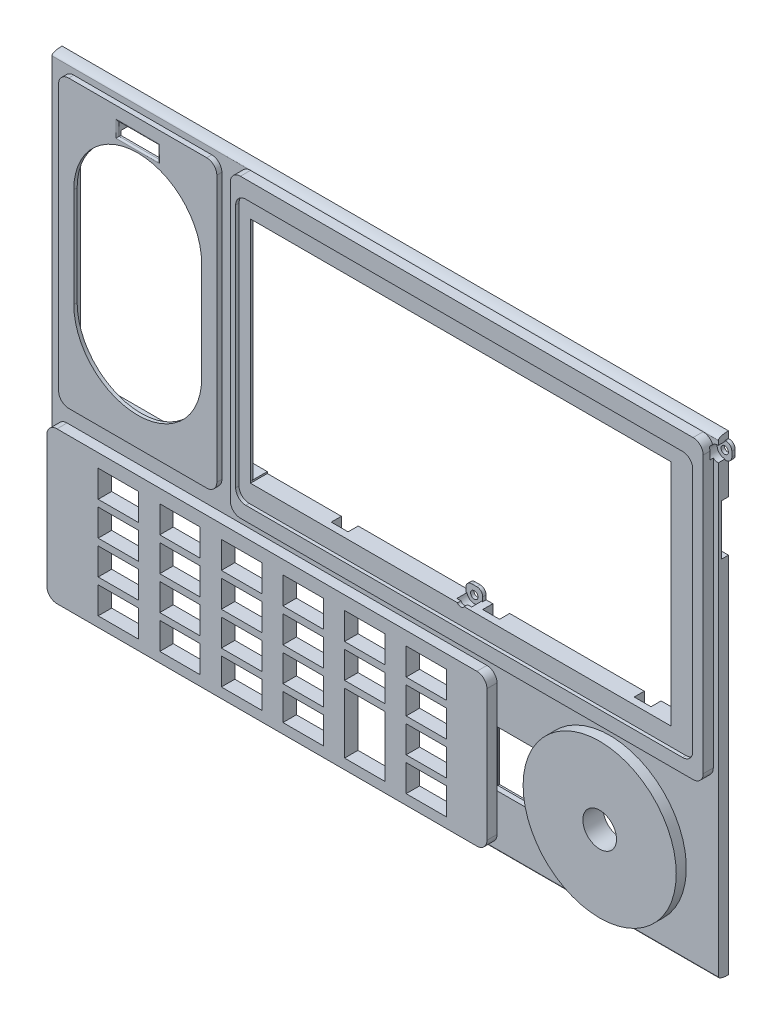
SolidWorks part; units mm, degrees
ref_plane "Front Plane" through (0, 0, 0) normal (0, 0, 1) x (1, 0, 0)
ref_plane "Top Plane" through (0, 0, 0) normal (0, 1, 0) x (1, 0, 0)
ref_plane "Right Plane" through (0, 0, 0) normal (1, 0, 0) x (0, 0, -1)
sketch "Sketch1" plane through (0, 0, 0) normal (0, 0, 1) x (1, 0, 0)
  line L1 (99, -70) -> (-99, -70)
  line L2 (99, -70) -> (99, 70)
  line L3 (99, 70) -> (-99, 70)
  line L4 (-99, -70) -> (-99, 70)
  line L5 (99, -70) -> (-99, 70) construction
  line L6 (99, 70) -> (-99, -70) construction
  point P0 (0, 0)
  dimension "D1" = 198
  dimension "D2" = 140
extrude "main_body" add sketch "Sketch1" along normal blind 3
fillet "long_corners" radius 3 2 edges at (0, 70, 3) (0, -70, 3) second distance 1 first distance on face at (0, 70, 1.5) first distance on face at (0, -70, 1.5)
sketch "Sketch2" plane through (0, 0, 3) normal (0, 0, 1) x (1, 0, 0)
  line L0 (-99, 24.75) -> (99, 24.75) construction
  line L1 (-99, 69) -> (-99, -69) construction
  line L2 (99, -69) -> (99, 69) construction
  line L3 (99, 69) -> (-99, 69) construction
  line L4 (-48.5, -17.75) -> (-95.5, -17.75)
  line L5 (-48.5, -17.75) -> (-48.5, 67.25)
  line L6 (-48.5, 67.25) -> (-95.5, 67.25)
  line L7 (-95.5, -17.75) -> (-95.5, 67.25)
  line L8 (-48.5, -17.75) -> (-95.5, 67.25) construction
  line L9 (-48.5, 67.25) -> (-95.5, -17.75) construction
  point P6 (-72, 24.75)
  dimension "D1" = 85
  dimension "D2" = 47
  dimension "D3" = 27
  dimension "D4" = 44.25
extrude "speaker" add sketch "Sketch2" along normal blind 1.5
fillet "speaker_corners" radius 3 4 edges at (-95.5, 67.25, 3.75) (-95.5, -17.75, 3.75) (-48.5, -17.75, 3.75) (-48.5, 67.25, 3.75)
sketch "Sketch19" plane through (0, 0, 4.5) normal (0, 0, 1) x (1, 0, 0)
  line L0 (-72, 67.25) -> (-72, -17.75) construction
  line L1 (-51.5, 67.25) -> (-92.5, 67.25) construction
  line L2 (-92.5, -17.75) -> (-51.5, -17.75) construction
  line L3 (-72, 9.75) -> (-72, 39.25) construction
  line L4 (-95.5, 64.25) -> (-95.5, -14.75) construction
  line L5 (-95.5, 24.75) -> (-48.5, 24.75) construction
  line L6 (-48.5, -14.75) -> (-48.5, 64.25) construction
  line L7 (-91, 9.75) -> (-91, 39.25)
  line L8 (-53, 9.75) -> (-53, 39.25)
  arc A0 (-91, 9.75) -> (-53, 9.75) centre (-72, 9.75) ccw
  arc A1 (-53, 39.25) -> (-91, 39.25) centre (-72, 39.25) ccw
  point P14 (-72, 24.5)
  point P19 (-72, -9.25)
  point P20 (-72, 58.25)
  dimension "D2" = 67.5
  dimension "D1" = 38
  dimension "D3" = 9
  dimension "D4" = 8.5
extrude "speaker_cut" cut sketch "Sketch19" against normal through all
sketch "Sketch21" plane through (0, 0, 0) normal (0, 0, -1) x (-1, 0, 0)
  line L0 (72, -9.25) -> (72, 58.25) construction
  line L2 (53, 9.75) -> (53, 39.25) construction
  line L3 (53, 24.5) -> (91, 24.5) construction
  line L4 (91, 39.25) -> (91, 9.75) construction
  line L5 (50.5, 60.5) -> (93.5, 60.5)
  line L6 (50.5, 60.5) -> (50.5, -11.5)
  line L7 (50.5, -11.5) -> (93.5, -11.5)
  line L8 (93.5, 60.5) -> (93.5, -11.5)
  line L9 (50.5, 60.5) -> (93.5, -11.5) construction
  line L10 (50.5, -11.5) -> (93.5, 60.5) construction
  arc A0 (53, 9.75) -> (91, 9.75) centre (72, 9.75) ccw construction
  arc A1 (91, 39.25) -> (53, 39.25) centre (72, 39.25) ccw construction
  point P14 (72, 24.5)
  dimension "D1" = 43
  dimension "D2" = 72
extrude "speaker_slot" cut sketch "Sketch21" against normal blind 3.5
sketch "Sketch3" plane through (0, 0, 3) normal (0, 0, 1) x (1, 0, 0)
  line L0 (-99, 25) -> (99, 25) construction
  line L1 (-99, 69) -> (-99, -69) construction
  line L2 (99, -69) -> (99, 69) construction
  line L4 (-48.5, -14.75) -> (-48.5, 64.25) construction
  line L5 (97.5, -19) -> (-43, -19)
  line L6 (97.5, -19) -> (97.5, 69)
  line L7 (97.5, 69) -> (-43, 69)
  line L8 (-43, -19) -> (-43, 69)
  line L9 (97.5, -19) -> (-43, 69) construction
  line L10 (97.5, 69) -> (-43, -19) construction
  line L11 (99, 70) -> (-99, 70) construction
  point P8 (27.25, 25)
  dimension "D1" = 1
  dimension "D2" = 88
  dimension "D3" = 140.5
  dimension "D4" = 1.5
  dimension "D5" = 5.5
extrude "lcd" add sketch "Sketch3" along normal blind 3
fillet "lcd_corners" radius 3 4 edges at (97.5, -19, 4.5) (-43, -19, 4.5)
sketch "Sketch9" plane through (0, 0, 6) normal (0, 0, 1) x (1, 0, 0)
  line L0 (-43, 24.5) -> (97.5, 24.5) construction
  line L1 (-43, 66) -> (-43, -16) construction
  line L2 (97.5, -16) -> (97.5, 66) construction
  line L3 (-40, -19) -> (94.5, -19) construction
  line L4 (94.4, -14.875) -> (-41.4, -14.875)
  line L5 (94.4, -14.875) -> (94.4, 63.875)
  line L6 (94.4, 63.875) -> (-41.4, 63.875)
  line L7 (-41.4, -14.875) -> (-41.4, 63.875)
  line L8 (94.4, -14.875) -> (-41.4, 63.875) construction
  line L9 (94.4, 63.875) -> (-41.4, -14.875) construction
  line L10 (94.5, 69) -> (-40, 69) construction
  line L11 (97.5, -16) -> (97.5, 66) construction
  point P6 (26.5, 24.5)
  dimension "D1" = 135.8
  dimension "D2" = 78.75
  dimension "D3" = 1.6
  dimension "D4" = 4.125
  dimension "D5" = 5.125
  dimension "D6" = 3.1
extrude "lcd_front" cut sketch "Sketch9" against normal blind 1
fillet "lcd_front_corners" radius 3 4 edges at (94.4, -14.875, 5.5) (94.4, 63.875, 5.5) (-41.4, 63.875, 5.5) (-41.4, -14.875, 5.5)
sketch "Sketch10" plane through (0, 0, 0) normal (0, 0, -1) x (-1, 0, 0)
  line L0 (-94.4, -11.875) -> (-94.4, 60.875) construction
  line L1 (-91.4, 63.875) -> (38.4, 63.875) construction
  line L2 (41.4, 63.875) -> (41.4, -14.875) construction
  line L3 (-94.4, 63.875) -> (41.4, 63.875) construction
  line L4 (38, -9.5) -> (-87, -9.5)
  line L5 (38, -9.5) -> (38, 58.5)
  line L6 (38, 58.5) -> (-87, 58.5)
  line L7 (-87, -9.5) -> (-87, 58.5)
  line L8 (-87, -9.5) -> (38, 58.5) construction
  line L9 (-87, 58.5) -> (38, -9.5) construction
  line L10 (-99, -70) -> (-99, 70) construction
  line L11 (-99, 70) -> (99, 70) construction
  line L13 (38.4, -14.875) -> (-91.4, -14.875) construction
  dimension "D1" = 125
  dimension "D2" = 68
  dimension "D3" = 12
  dimension "D4" = 3.4
  dimension "D5" = 11.5
  dimension "D6" = 5.375
  dimension "D7" = 7.4
  dimension "D8" = 5.375
  dimension "D9" = 5.375
extrude "lcd_back" cut sketch "Sketch10" against normal through all
sketch "Sketch56" plane through (0, 0, 0) normal (0, 0, -1) x (-1, 0, 0)
  line L0 (-87, -9.5) -> (38, -9.5) construction
  line L1 (-79, -9.5) -> (-74, -9.5)
  line L2 (-79, -9.5) -> (-79, -12.5)
  line L3 (-79, -12.5) -> (-74, -12.5)
  line L4 (-74, -9.5) -> (-74, -12.5)
  line L5 (38, 58.5) -> (-87, 58.5) construction
  line L6 (-34, -9.5) -> (-29, -9.5)
  line L7 (-34, -9.5) -> (-34, -12.5)
  line L8 (-34, -12.5) -> (-29, -12.5)
  line L9 (-29, -9.5) -> (-29, -12.5)
  line L10 (11, -9.5) -> (16, -9.5)
  line L11 (11, -9.5) -> (11, -12.5)
  line L12 (11, -12.5) -> (16, -12.5)
  line L13 (16, -9.5) -> (16, -12.5)
  line L14 (-79, 58.5) -> (-74, 58.5)
  line L15 (-79, 58.5) -> (-79, 61.5)
  line L16 (-79, 61.5) -> (-74, 61.5)
  line L17 (-74, 58.5) -> (-74, 61.5)
  line L18 (38, -9.5) -> (38, 58.5) construction
  line L19 (-34, 58.5) -> (-29, 58.5)
  line L20 (-34, 58.5) -> (-34, 61.5)
  line L21 (-34, 61.5) -> (-29, 61.5)
  line L22 (-29, 58.5) -> (-29, 61.5)
  line L23 (11, 58.5) -> (16, 58.5)
  line L24 (11, 58.5) -> (11, 61.5)
  line L25 (11, 61.5) -> (16, 61.5)
  line L26 (16, 58.5) -> (16, 61.5)
  line L27 (38, 58) -> (42, 58)
  line L28 (38, 58) -> (38, -9)
  line L29 (38, -9) -> (42, -9)
  line L30 (42, 58) -> (42, -9)
  line L31 (-99, -70) -> (-99, 70) construction
  line L32 (-99, 70) -> (99, 70) construction
  point P34 (-29, -11)
  dimension "D1" = 5
  dimension "D2" = 5
  dimension "D3" = 5
  dimension "D4" = 5
  dimension "D5" = 5
  dimension "D6" = 5
  dimension "D7" = 67
  dimension "D8" = 4
  dimension "D9" = 3
  dimension "D10" = 3
  dimension "D11" = 3
  dimension "D12" = 3
  dimension "D13" = 3
  dimension "D14" = 3
  dimension "D15" = 40
  dimension "D16" = 40
  dimension "D17" = 20
  dimension "D18" = 20
  dimension "D19" = 40
  dimension "D20" = 40
  dimension "D21" = 12
extrude "lcd_glue_points" cut sketch "Sketch56" against normal blind 3
sketch "Sketch4" plane through (0, 0, 3) normal (0, 0, 1) x (1, 0, 0)
  line L0 (-99, -45.75) -> (99, -45.75) construction
  line L1 (-99, 69) -> (-99, -69) construction
  line L2 (99, -69) -> (99, 69) construction
  line L4 (-92.5, -17.75) -> (-51.5, -17.75) construction
  line L5 (33.25, -68.25) -> (-97.5, -68.25)
  line L6 (33.25, -68.25) -> (33.25, -23.25)
  line L7 (33.25, -23.25) -> (-97.5, -23.25)
  line L8 (-97.5, -68.25) -> (-97.5, -23.25)
  line L9 (33.25, -68.25) -> (-97.5, -23.25) construction
  line L10 (33.25, -23.25) -> (-97.5, -68.25) construction
  line L11 (-99, -70) -> (99, -70) construction
  point P8 (-32.125, -45.75)
  dimension "D1" = 1.75
  dimension "D2" = 130.75
  dimension "D3" = 45
  dimension "D4" = 1.5
  dimension "D5" = 5.5
extrude "keypad" add sketch "Sketch4" along normal blind 3
fillet "keypad_corners" radius 3 4 edges at (-97.5, -68.25, 4.5) (33.25, -68.25, 4.5) (33.25, -23.25, 4.5) (-97.5, -23.25, 4.5)
sketch "Sketch25" plane through (0, 0, 6) normal (0, 0, 1) x (1, 0, 0)
  line L0 (-97.5, -31.25) -> (33.25, -31.25) construction
  line L1 (30.25, -23.25) -> (-94.5, -23.25) construction
  line L2 (-94.5, -68.25) -> (30.25, -68.25) construction
  line L3 (-76.25, -23.25) -> (-76.25, -68.25) construction
  line L5 (-33.65, -65.25) -> (33.25, -65.25) construction
  line L6 (-97.5, -26.25) -> (-97.5, -65.25) construction
  line L11 (33.25, -65.25) -> (33.25, -26.25) construction
  line L12 (-57.95, -23.25) -> (-57.95, -68.25) construction
  line L13 (-97.5, -41.25) -> (33.25, -41.25) construction
  line L14 (30.25, -23.25) -> (-94.5, -23.25) construction
  line L15 (-39.65, -23.25) -> (-39.65, -68.25) construction
  line L16 (-94.5, -68.25) -> (30.25, -68.25) construction
  line L17 (-70.25, -35.25) -> (-82.25, -35.25)
  line L18 (-21.35, -23.25) -> (-21.35, -68.25) construction
  line L19 (-97.5, -51.25) -> (33.25, -51.25) construction
  line L20 (-3.05, -23.25) -> (-3.05, -68.25) construction
  line L21 (-70.25, -35.25) -> (-70.25, -27.25)
  line L22 (15.25, -23.25) -> (15.25, -68.25) construction
  line L23 (-97.5, -26.25) -> (-97.5, -65.25) construction
  line L24 (-97.5, -61.25) -> (33.25, -61.25) construction
  line L25 (-70.25, -27.25) -> (-82.25, -27.25)
  line L26 (-82.25, -35.25) -> (-82.25, -27.25)
  line L27 (-70.25, -35.25) -> (-82.25, -27.25) construction
  line L28 (-70.25, -27.25) -> (-82.25, -35.25) construction
  line L29 (-70.25, -45.25) -> (-82.25, -45.25)
  line L30 (-70.25, -45.25) -> (-70.25, -37.25)
  line L31 (-70.25, -37.25) -> (-82.25, -37.25)
  line L32 (-82.25, -45.25) -> (-82.25, -37.25)
  line L33 (-70.25, -45.25) -> (-82.25, -37.25) construction
  line L34 (-70.25, -37.25) -> (-82.25, -45.25) construction
  line L35 (-70.25, -55.25) -> (-82.25, -55.25)
  line L36 (-70.25, -55.25) -> (-70.25, -47.25)
  line L37 (-70.25, -47.25) -> (-82.25, -47.25)
  line L38 (-82.25, -55.25) -> (-82.25, -47.25)
  line L39 (-70.25, -55.25) -> (-82.25, -47.25) construction
  line L40 (-70.25, -47.25) -> (-82.25, -55.25) construction
  line L41 (-70.25, -65.25) -> (-82.25, -65.25)
  line L42 (-70.25, -65.25) -> (-70.25, -57.25)
  line L43 (-70.25, -57.25) -> (-82.25, -57.25)
  line L44 (-82.25, -65.25) -> (-82.25, -57.25)
  line L45 (-70.25, -65.25) -> (-82.25, -57.25) construction
  line L46 (-70.25, -57.25) -> (-82.25, -65.25) construction
  line L47 (-51.95, -35.25) -> (-63.95, -35.25)
  line L48 (-51.95, -35.25) -> (-51.95, -27.25)
  line L49 (-51.95, -27.25) -> (-63.95, -27.25)
  line L50 (-63.95, -35.25) -> (-63.95, -27.25)
  line L51 (-51.95, -35.25) -> (-63.95, -27.25) construction
  line L52 (-51.95, -27.25) -> (-63.95, -35.25) construction
  line L53 (-51.95, -45.25) -> (-63.95, -45.25)
  line L54 (-51.95, -45.25) -> (-51.95, -37.25)
  line L55 (-51.95, -37.25) -> (-63.95, -37.25)
  line L56 (-63.95, -45.25) -> (-63.95, -37.25)
  line L57 (-51.95, -45.25) -> (-63.95, -37.25) construction
  line L58 (-51.95, -37.25) -> (-63.95, -45.25) construction
  line L59 (-51.95, -55.25) -> (-63.95, -55.25)
  line L60 (-51.95, -55.25) -> (-51.95, -47.25)
  line L61 (-51.95, -47.25) -> (-63.95, -47.25)
  line L62 (-63.95, -55.25) -> (-63.95, -47.25)
  line L63 (-51.95, -55.25) -> (-63.95, -47.25) construction
  line L64 (-51.95, -47.25) -> (-63.95, -55.25) construction
  line L65 (-51.95, -65.25) -> (-63.95, -65.25)
  line L66 (-51.95, -65.25) -> (-51.95, -57.25)
  line L67 (-51.95, -57.25) -> (-63.95, -57.25)
  line L68 (-63.95, -65.25) -> (-63.95, -57.25)
  line L69 (-51.95, -65.25) -> (-63.95, -57.25) construction
  line L70 (-51.95, -57.25) -> (-63.95, -65.25) construction
  line L71 (-33.65, -35.25) -> (-45.65, -35.25)
  line L72 (-33.65, -35.25) -> (-33.65, -27.25)
  line L73 (-33.65, -27.25) -> (-45.65, -27.25)
  line L74 (-45.65, -35.25) -> (-45.65, -27.25)
  line L75 (-33.65, -35.25) -> (-45.65, -27.25) construction
  line L76 (-33.65, -27.25) -> (-45.65, -35.25) construction
  line L77 (-33.65, -45.25) -> (-45.65, -45.25)
  line L78 (-33.65, -45.25) -> (-33.65, -37.25)
  line L79 (-33.65, -37.25) -> (-45.65, -37.25)
  line L80 (-45.65, -45.25) -> (-45.65, -37.25)
  line L81 (-33.65, -45.25) -> (-45.65, -37.25) construction
  line L82 (-33.65, -37.25) -> (-45.65, -45.25) construction
  line L83 (-33.65, -55.25) -> (-45.65, -55.25)
  line L84 (-33.65, -55.25) -> (-33.65, -47.25)
  line L85 (-33.65, -47.25) -> (-45.65, -47.25)
  line L86 (-45.65, -55.25) -> (-45.65, -47.25)
  line L87 (-33.65, -55.25) -> (-45.65, -47.25) construction
  line L88 (-33.65, -47.25) -> (-45.65, -55.25) construction
  line L89 (-33.65, -65.25) -> (-45.65, -65.25)
  line L90 (-33.65, -65.25) -> (-33.65, -57.25)
  line L91 (-33.65, -57.25) -> (-45.65, -57.25)
  line L92 (-45.65, -65.25) -> (-45.65, -57.25)
  line L93 (-33.65, -65.25) -> (-45.65, -57.25) construction
  line L94 (-33.65, -57.25) -> (-45.65, -65.25) construction
  line L95 (-15.35, -35.25) -> (-27.35, -35.25)
  line L96 (-15.35, -35.25) -> (-15.35, -27.25)
  line L97 (-15.35, -27.25) -> (-27.35, -27.25)
  line L98 (-27.35, -35.25) -> (-27.35, -27.25)
  line L99 (-15.35, -35.25) -> (-27.35, -27.25) construction
  line L100 (-15.35, -27.25) -> (-27.35, -35.25) construction
  line L101 (-15.35, -45.25) -> (-27.35, -45.25)
  line L102 (-15.35, -45.25) -> (-15.35, -37.25)
  line L103 (-15.35, -37.25) -> (-27.35, -37.25)
  line L104 (-27.35, -45.25) -> (-27.35, -37.25)
  line L105 (-15.35, -45.25) -> (-27.35, -37.25) construction
  line L106 (-15.35, -37.25) -> (-27.35, -45.25) construction
  line L111 (-15.35, -55.25) -> (-27.35, -55.25)
  line L112 (-15.35, -55.25) -> (-15.35, -47.25)
  line L113 (-15.35, -47.25) -> (-27.35, -47.25)
  line L114 (-27.35, -55.25) -> (-27.35, -47.25)
  line L115 (-15.35, -55.25) -> (-27.35, -47.25) construction
  line L116 (-15.35, -47.25) -> (-27.35, -55.25) construction
  line L117 (-15.35, -65.25) -> (-27.35, -65.25)
  line L118 (-15.35, -65.25) -> (-15.35, -57.25)
  line L119 (-15.35, -57.25) -> (-27.35, -57.25)
  line L120 (-27.35, -65.25) -> (-27.35, -57.25)
  line L121 (-15.35, -65.25) -> (-27.35, -57.25) construction
  line L122 (-15.35, -57.25) -> (-27.35, -65.25) construction
  line L127 (2.95, -35.25) -> (-9.05, -35.25)
  line L128 (2.95, -35.25) -> (2.95, -27.25)
  line L129 (2.95, -27.25) -> (-9.05, -27.25)
  line L130 (-9.05, -35.25) -> (-9.05, -27.25)
  line L131 (2.95, -35.25) -> (-9.05, -27.25) construction
  line L132 (2.95, -27.25) -> (-9.05, -35.25) construction
  line L133 (21.25, -35.25) -> (9.25, -35.25)
  line L134 (21.25, -35.25) -> (21.25, -27.25)
  line L135 (21.25, -27.25) -> (9.25, -27.25)
  line L136 (9.25, -35.25) -> (9.25, -27.25)
  line L137 (21.25, -35.25) -> (9.25, -27.25) construction
  line L138 (21.25, -27.25) -> (9.25, -35.25) construction
  line L139 (2.95, -45.25) -> (-9.05, -45.25)
  line L140 (2.95, -45.25) -> (2.95, -37.25)
  line L141 (2.95, -37.25) -> (-9.05, -37.25)
  line L142 (-9.05, -45.25) -> (-9.05, -37.25)
  line L143 (2.95, -45.25) -> (-9.05, -37.25) construction
  line L144 (2.95, -37.25) -> (-9.05, -45.25) construction
  line L145 (21.25, -45.25) -> (9.25, -45.25)
  line L146 (21.25, -45.25) -> (21.25, -37.25)
  line L147 (21.25, -37.25) -> (9.25, -37.25)
  line L148 (9.25, -45.25) -> (9.25, -37.25)
  line L149 (21.25, -45.25) -> (9.25, -37.25) construction
  line L150 (21.25, -37.25) -> (9.25, -45.25) construction
  line L151 (21.25, -55.25) -> (9.25, -55.25)
  line L152 (21.25, -55.25) -> (21.25, -47.25)
  line L153 (21.25, -47.25) -> (9.25, -47.25)
  line L154 (9.25, -55.25) -> (9.25, -47.25)
  line L155 (21.25, -55.25) -> (9.25, -47.25) construction
  line L156 (21.25, -47.25) -> (9.25, -55.25) construction
  line L157 (21.25, -65.25) -> (9.25, -65.25)
  line L158 (21.25, -65.25) -> (21.25, -57.25)
  line L159 (21.25, -57.25) -> (9.25, -57.25)
  line L160 (9.25, -65.25) -> (9.25, -57.25)
  line L161 (21.25, -65.25) -> (9.25, -57.25) construction
  line L162 (21.25, -57.25) -> (9.25, -65.25) construction
  line L163 (2.95, -65.25) -> (-9.05, -65.25)
  line L164 (2.95, -65.25) -> (2.95, -47.25)
  line L165 (2.95, -47.25) -> (-9.05, -47.25)
  line L166 (-9.05, -65.25) -> (-9.05, -47.25)
  line L167 (2.95, -65.25) -> (-9.05, -47.25) construction
  line L168 (2.95, -47.25) -> (-9.05, -65.25) construction
  point P34 (-76.25, -31.25)
  point P39 (-76.25, -41.25)
  point P44 (-76.25, -51.25)
  point P49 (-76.25, -61.25)
  point P54 (-57.95, -31.25)
  point P59 (-57.95, -41.25)
  point P64 (-57.95, -51.25)
  point P69 (-57.95, -61.25)
  point P74 (-39.65, -31.25)
  point P79 (-39.65, -41.25)
  point P84 (-39.65, -51.25)
  point P89 (-39.65, -61.25)
  point P94 (-21.35, -31.25)
  point P99 (-21.35, -41.25)
  point P104 (-21.35, -51.25)
  point P109 (-21.35, -61.25)
  point P114 (-3.05, -31.25)
  point P119 (15.25, -31.25)
  point P124 (-3.05, -41.25)
  point P129 (15.25, -41.25)
  point P134 (15.25, -51.25)
  point P139 (15.25, -61.25)
  point P144 (-3.05, -56.25)
  dimension "D1" = 18
  dimension "D2" = 18.3
  dimension "D3" = 18.3
  dimension "D4" = 18.3
  dimension "D5" = 18.3
  dimension "D6" = 18.3
  dimension "D7" = 21.25
  dimension "D8" = 8
  dimension "D9" = 10
  dimension "D10" = 10
  dimension "D11" = 10
  dimension "D12" = 7
  dimension "D13" = 12
  dimension "D14" = 12
  dimension "D15" = 12
  dimension "D16" = 12
  dimension "D17" = 12
  dimension "D18" = 12
  dimension "D19" = 12
  dimension "D20" = 12
  dimension "D21" = 12
  dimension "D22" = 12
  dimension "D23" = 12
  dimension "D24" = 12
  dimension "D25" = 12
  dimension "D26" = 12
  dimension "D27" = 12
  dimension "D28" = 12
  dimension "D29" = 12
  dimension "D30" = 12
  dimension "D31" = 12
  dimension "D32" = 12
  dimension "D33" = 12
  dimension "D34" = 12
  dimension "D35" = 12
  dimension "D36" = 8
  dimension "D37" = 8
  dimension "D38" = 8
  dimension "D39" = 8
  dimension "D40" = 8
  dimension "D41" = 8
  dimension "D42" = 18
  dimension "D43" = 8
  dimension "D44" = 8
  dimension "D45" = 8
  dimension "D46" = 8
  dimension "D47" = 8
  dimension "D48" = 8
  dimension "D49" = 8
  dimension "D50" = 8
  dimension "D51" = 8
  dimension "D52" = 8
  dimension "D53" = 8
  dimension "D54" = 8
  dimension "D55" = 8
  dimension "D56" = 8
  dimension "D57" = 8
  dimension "D58" = 8
  dimension "D59" = 5
extrude "keypad_cuts_0.8" cut sketch "Sketch25" against normal through all
sketch "Sketch5" plane through (0, 0, 3) normal (0, 0, 1) x (1, 0, 0)
  line L0 (33.25, -45.75) -> (99, -45.75) construction
  line L1 (33.25, -65.25) -> (33.25, -26.25) construction
  line L2 (99, -69) -> (99, 69) construction
  circle A0 centre (66.75, -45.75) radius 22.75
  dimension "D1" = 45.5
  dimension "D2" = 32.25
  dimension "D3" = 33.5
extrude "vfo" add sketch "Sketch5" along normal blind 3
sketch "Sketch7" plane through (0, 0, 6) normal (0, 0, 1) x (1, 0, 0)
  line L0 (44, -45.75) -> (89.5, -45.75) construction
  line L1 (66.75, -23) -> (66.75, -68.5) construction
  circle A0 centre (66.75, -45.75) radius 22.75 construction
  circle A1 centre (66.75, -45.75) radius 22.75 construction
  circle A2 centre (66.75, -45.75) radius 5
  dimension "D1" = 10
extrude "vfo_encoder_knob_cut" cut sketch "Sketch7" against normal through all
sketch "esp32" plane through (0, 0, 0) normal (0, 0, -1) x (-1, 0, 0)
  line L0 (99, -70) -> (-99, -70) construction
  line L1 (-50.5, -37.5) -> (-32, -37.5)
  line L2 (-50.5, -37.5) -> (-50.5, -54)
  line L3 (-50.5, -54) -> (-32, -54)
  line L4 (-32, -37.5) -> (-32, -54)
  line L5 (-99, -70) -> (-99, 70) construction
  dimension "D1" = 16
  dimension "D2" = 48.5
  dimension "D3" = 16.5
  dimension "D4" = 18.5
extrude "esp32_can_cut" cut sketch "esp32" against normal blind 3
sketch "Sketch47" plane through (0, 0, 0) normal (0, 0, -1) x (-1, 0, 0)
  line L0 (-50.5, -54) -> (-32, -54) construction
  line L1 (-31, -55) -> (-58, -55)
  line L2 (-31, -55) -> (-31, -36.5)
  line L3 (-31, -36.5) -> (-58, -36.5)
  line L4 (-58, -55) -> (-58, -36.5)
  line L5 (-31, -55) -> (-58, -36.5) construction
  line L6 (-31, -36.5) -> (-58, -55) construction
  line L7 (-50.5, -37.5) -> (-50.5, -54) construction
  point P0 (-44.5, -45.75)
  dimension "D1" = 27
  dimension "D2" = 18.5
  dimension "D3" = 1
  dimension "D4" = 7.5
extrude "esp32_ex_cut" cut sketch "Sketch47" against normal blind 1.5
sketch "Sketch49" plane through (0, 0, 0) normal (0, 0, -1) x (-1, 0, 0)
  line L0 (72, 61.25) -> (72, 67.25) construction
  line L3 (51.5, 67.25) -> (92.5, 67.25) construction
  line L4 (78, 59.25) -> (66, 59.25)
  line L5 (78, 59.25) -> (78, 63.25)
  line L6 (78, 63.25) -> (66, 63.25)
  line L7 (66, 59.25) -> (66, 63.25)
  line L8 (78, 59.25) -> (66, 63.25) construction
  line L9 (78, 63.25) -> (66, 59.25) construction
  point P6 (72, 61.25)
  dimension "D1" = 12
  dimension "D2" = 4
  dimension "D3" = 6
extrude "amb_sensor" cut sketch "Sketch49" against normal through all
fillet "amb_corners" radius 0.5 4 edges at (-66, 61.25, 4.5) (-72, 63.25, 4.5) (-78, 61.25, 4.5) (-72, 59.25, 4.5)
sketch "Sketch55" plane through (0, 0, 0) normal (0, 0, -1) x (-1, 0, 0)
  line L0 (-99, -70) -> (-99, 70) construction
  line L5 (-89, 69.5) -> (-77, 69.5)
  line L6 (-89, 69.5) -> (-89, 59)
  line L11 (-89, 59) -> (-77, 59)
  line L12 (-77, 69.5) -> (-77, 59)
  line L13 (94.5, 48) -> (99, 48)
  line L14 (94.5, 48) -> (94.5, 33)
  line L15 (94.5, 33) -> (99, 33)
  line L16 (99, 48) -> (99, 33)
  line L17 (94.5, 48) -> (99, 33) construction
  line L18 (94.5, 33) -> (99, 48) construction
  line L23 (99, 65.5) -> (-99, 65.5) construction
  line L24 (99, -8.5) -> (-99, -8.5) construction
  line L35 (-99, -68) -> (99, -68) construction
  line L36 (99, -70) -> (-99, -70) construction
  line L42 (-99, 53) -> (-93, 53)
  line L43 (-99, 53) -> (-99, 38)
  line L44 (-99, 70) -> (99, 70) construction
  line L45 (-99, 38) -> (-93, 38)
  line L46 (99, 70) -> (99, -70) construction
  line L47 (-93, 53) -> (-93, 38)
  circle A0 centre (85, 65.5) radius 2.75
  circle A1 centre (49.5, 65.5) radius 2.75
  circle A2 centre (-24.5, 65.5) radius 2.75
  circle A4 centre (49.5, -8.5) radius 2.25
  circle A6 centre (-68, -68) radius 2.25
  circle A7 centre (-1, -68) radius 2.25
  circle A9 centre (-32, 65.5) radius 2.75
  point P10 (96.75, 40.5)
  dimension "D7" = 5.5
  dimension "D8" = 5.5
  dimension "D9" = 5.5
  dimension "D13" = 5.5
  dimension "D18" = 2
  dimension "D19" = 4.5
  dimension "D21" = 4.5
  dimension "D22" = 4.5
  dimension "D1" = 12
  dimension "D3" = 10.5
  dimension "D4" = 0.5
  dimension "D5" = 10
  dimension "D6" = 4.5
  dimension "D10" = 14
  dimension "D11" = 49.5
  dimension "D12" = 123.5
  dimension "D14" = 7.5
  dimension "D15" = 61.5
  dimension "D24" = 100
  dimension "D25" = 15
  dimension "D26" = 4.5
  dimension "D27" = 0
  dimension "D28" = 22
  dimension "D29" = 49.5
  dimension "D30" = 67
  dimension "D31" = 6
  dimension "D32" = 15
  dimension "D33" = 0
  dimension "D34" = 17
extrude "conn_cutouts" cut sketch "Sketch55" against normal blind 2
fillet "Fillet1" radius 2 1 edges at (-38, 24.5, 3)
fillet "Fillet2" radius 5 1 edges at (-42, 24.5, 0)
sketch "Sketch57" plane through (0, 0, 0) normal (0, 0, -1) x (-1, 0, 0)
  line L0 (99, 70) -> (99, 48) construction
  line L1 (-24, -22) -> (89, -22)
  line L2 (-24, -22) -> (-24, -67.5)
  line L3 (-24, -67.5) -> (89, -67.5)
  line L4 (89, -22) -> (89, -67.5)
  line L5 (99, -70) -> (0.0308, -70) construction
  dimension "D1" = 113
  dimension "D2" = 45.5
  dimension "D3" = 10
  dimension "D4" = 2.5
extrude "keyboard_back" cut sketch "Sketch57" against normal blind 2
sketch "Sketch58" plane through (0, -9.5, 0) normal (0, 1, 0) x (1, 0, 0)
  line L1 (27, -1) -> (22, -1)
  line L2 (27, -1) -> (27, 0)
  line L3 (27, 0) -> (22, 0)
  line L4 (22, -1) -> (22, 0)
  line L5 (27, -1) -> (22, 0) construction
  line L6 (27, 0) -> (22, -1) construction
  line L7 (29, -3) -> (29, 0) construction
  line L9 (29, 0) -> (-11, 0) construction
  point P0 (24.5, -0.5)
  dimension "D1" = 1
  dimension "D2" = 5
  dimension "D3" = 2
  dimension "D4" = 0
extrude "behind_lcd_screew_mount" add sketch "Sketch58" along normal blind 3
sketch "Sketch59" plane through (-99, 0, 0) normal (-1, 0, 0) x (0, 0, 1)
  line L0 (0, 70) -> (0, 48) construction
  line L1 (0, -66.5) -> (1, -66.5)
  line L2 (0, -66.5) -> (0, -69.5)
  line L3 (0, -69.5) -> (1, -69.5)
  line L4 (1, -66.5) -> (1, -69.5)
  dimension "D1" = 1
  dimension "D2" = 3
  dimension "D3" = 66.5
extrude "keyb_screw_mount" add sketch "Sketch59" along normal blind 1
sketch "Sketch60" plane through (99, 0, 0) normal (1, 0, 0) x (0, 0, -1)
  line L0 (0, -70) -> (0, 38) construction
  line L1 (0, 68) -> (-1, 68)
  line L2 (0, 68) -> (0, 63)
  line L3 (0, 63) -> (-1, 63)
  line L4 (-1, 68) -> (-1, 63)
  dimension "D1" = 63
  dimension "D2" = 5
  dimension "D3" = 1
extrude "right_corner_screw_mount" add sketch "Sketch60" along normal blind 2
sketch "Sketch61" plane through (0, 0, 0) normal (0, 0, -1) x (-1, 0, 0)
  line L0 (-99, 70) -> (99, 70) construction
  line L1 (-99, 68) -> (-99, 70) construction
  line L2 (-99, -9) -> (99, -9) construction
  line L5 (-99, -70) -> (-99, 38) construction
  line L6 (99, 70) -> (99, 48) construction
  line L7 (-2.0308, -70) -> (-66.9692, -70) construction
  line L8 (99, -69.5) -> (99, -70) construction
  line L9 (99, -70) -> (0.0308, -70) construction
  circle A0 centre (-98.9, 65.5) radius 1.1
  circle A1 centre (-24.5, -9) radius 1.1
  circle A2 centre (98, -68) radius 1.1
  dimension "D1" = 2.2
  dimension "D6" = 2.2
  dimension "D9" = 2.2
  dimension "D2" = 4.5
  dimension "D3" = 0.1
  dimension "D4" = 61
  dimension "D5" = 123.5
  dimension "D7" = 1
  dimension "D8" = 2
extrude "ui_screws" cut sketch "Sketch61" against normal through all
sketch "Sketch62" plane through (0, 0, 6) normal (0, 0, 1) x (1, 0, 0)
  line L0 (97.8, 65.5) -> (100, 65.5) construction
  line L1 (-98, -66.9) -> (-98, -69.1) construction
  line L2 (98.9, 66.6) -> (98.9, 64.4) construction
  line L4 (-96.9, -68) -> (-99.1, -68) construction
  circle A0 centre (24.5, -9) radius 2.25
  arc A1 (99, 66.5954) -> (99, 64.4046) centre (98.9, 65.5) ccw construction
  arc A2 (99, 64.4046) -> (99, 66.5954) centre (98.9, 65.5) ccw construction
  circle A3 centre (98.9, 65.5) radius 2.25
  arc A4 (-97.5417, -69) -> (-99, -67.5417) centre (-98, -68) ccw construction
  arc A5 (-98.4583, -69) -> (-97.5417, -69) centre (-98, -68) ccw construction
  arc A6 (-99, -67.5417) -> (-99, -68.4583) centre (-98, -68) ccw construction
  circle A7 centre (-98, -68) radius 2.25
  dimension "D1" = 4.5
  dimension "D2" = 4.5
  dimension "D3" = 4.5
extrude "ui_screw_head" cut sketch "Sketch62" against normal blind 3 from offset 2 offset against normal yes
fillet "ui_screw_mount_corners" radius 1.75 6 edges at (-100, -66.5, 0.5) (-100, -69.5, 0.5) (101, 63, 0.5) (101, 68, 0.5) (22, -6.5, 0.5) (27, -6.5, 0.5)
